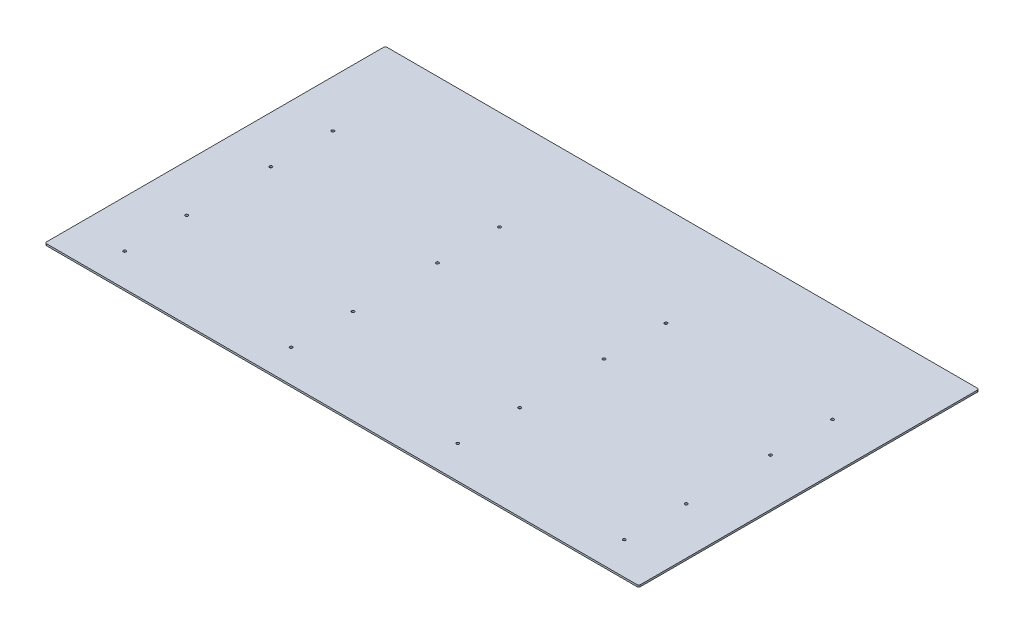
SolidWorks part; units mm, degrees
material "PE High Density"
ref_plane "Front Plane" through (0, 0, 0) normal (0, 0, 1) x (1, 0, 0)
ref_plane "Top Plane" through (0, 0, 0) normal (0, 1, 0) x (1, 0, 0)
ref_plane "Right Plane" through (0, 0, 0) normal (1, 0, 0) x (0, 0, -1)
sketch "Sketch1" plane through (0, 0, 0) normal (0, 1, 0) x (1, 0, 0)
  line L1 (-517.525, -298.45) -> (517.525, -298.45)
  line L2 (-520.7, -295.275) -> (-520.7, 295.275)
  line L3 (-517.525, 298.45) -> (517.525, 298.45)
  line L4 (520.7, -295.275) -> (520.7, 295.275)
  line L5 (-520.7, -298.45) -> (520.7, 298.45) construction
  line L6 (-520.7, 298.45) -> (520.7, -298.45) construction
  arc A0 (517.525, 298.45) -> (520.7, 295.275) centre (517.525, 295.275) cw
  arc A1 (517.525, -298.45) -> (520.7, -295.275) centre (517.525, -295.275) ccw
  arc A2 (-517.525, -298.45) -> (-520.7, -295.275) centre (-517.525, -295.275) cw
  arc A3 (-520.7, 295.275) -> (-517.525, 298.45) centre (-517.525, 295.275) cw
  point P0 (0, 0)
  dimension "D3" = 3.175
  dimension "D1" = 1041.4
  dimension "D2" = 596.9
extrude "Boss-Extrude1" add sketch "Sketch1" along normal blind 3.175
sketch "Sketch2" plane through (0, 0, 0) normal (0, -1, 0) x (1, 0, 0)
  line L0 (-517.525, 298.45) -> (517.525, 298.45) construction
  point P0 (-438.15, 241.2453)
  point P1 (-438.15, 132.5333)
  point P3 (-146.05, 241.2453)
  point P5 (-146.05, 132.5333)
  point P7 (146.05, 241.2453)
  point P9 (146.05, 132.5333)
  point P11 (438.15, 241.2453)
  point P13 (438.15, 132.5333)
  point P15 (438.15, -15.2947)
  point P17 (438.15, -124.0067)
  point P19 (146.05, -15.2947)
  point P21 (146.05, -124.0067)
  point P23 (-146.05, -15.2947)
  point P25 (-146.05, -124.0067)
  point P27 (-438.15, -15.2947)
  point P29 (-438.15, -124.0067)
  dimension "D1" = 108.712
  dimension "D2" = 108.712
  dimension "D3" = 147.828
  dimension "D4" = 57.2047
  dimension "D5" = 292.1
  dimension "D6" = 292.1
  dimension "D7" = 146.05
  dimension "D8" = 146.05
hole_wizard "#10 (0.1935) Diameter Hole1" positions "3DSketch1" profile "Sketch3" hole size "#10" standard "ANSI Inch" end condition through all
sketch3d "3DSketch1"
  point P0 (-438.15, 0, 241.2453)
  point P3 (-438.15, 0, 132.5333)
  point P6 (-146.05, 0, 241.2453)
  point P9 (-146.05, 0, 132.5333)
  point P12 (146.05, 0, 241.2453)
  point P15 (146.05, 0, 132.5333)
  point P18 (438.15, 0, 241.2453)
  point P21 (438.15, 0, 132.5333)
  point P24 (438.15, 0, -15.2947)
  point P27 (438.15, 0, -124.0067)
  point P30 (146.05, 0, -15.2947)
  point P33 (146.05, 0, -124.0067)
  point P36 (-146.05, 0, -124.0067)
  point P39 (-146.05, 0, -15.2947)
  point P42 (-438.15, 0, -15.2947)
  point P45 (-438.15, 0, -124.0067)
sketch "Sketch3" plane through (-438.15, 0, 241.2453) normal (1, 0, 0) x (0, 0, -1)
  line L0 (0, 0) -> (0, 3.175)
  line L1 (0, 3.175) -> (2.4574, 3.175)
  line L2 (2.4574, 3.175) -> (2.4574, 0)
  line L5 (2.4574, 0) -> (0, 0)
  line L11 (0, -6.35) -> (0, 107.95) construction
  dimension "Thru Hole Dia." = 4.9149
  dimension "Thru Hole Depth" = 3.175
